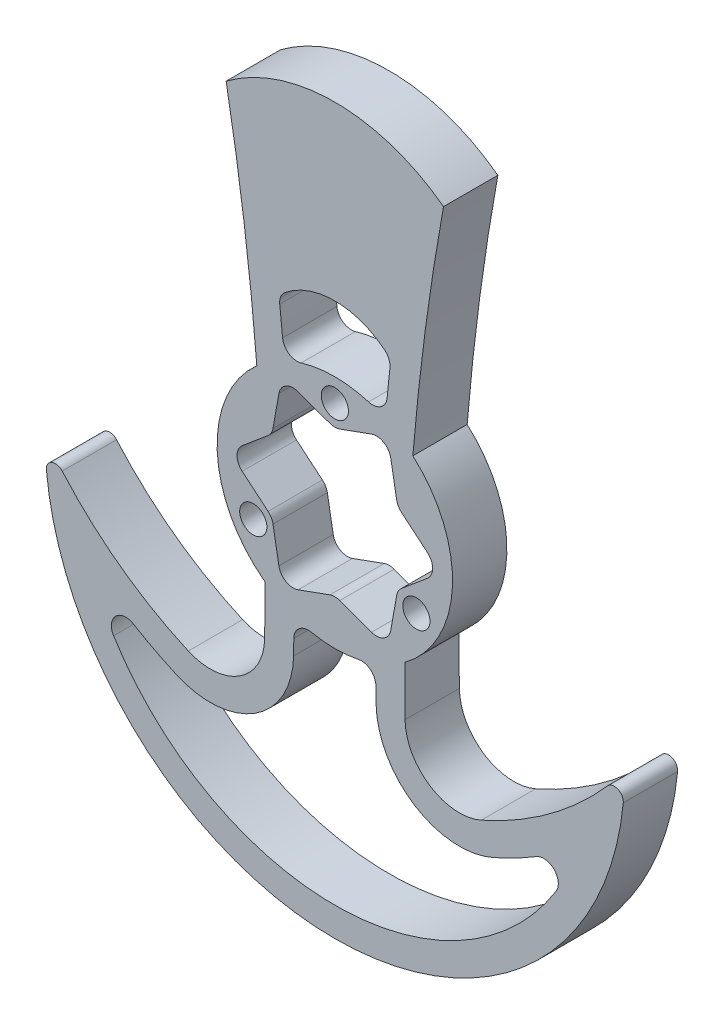
SolidWorks part; units mm, degrees
material "AISI 4340 Steel, annealed"
ref_plane "Front Plane" through (0, 0, 0) normal (0, 0, 1) x (1, 0, 0)
ref_plane "Top Plane" through (0, 0, 0) normal (0, 1, 0) x (1, 0, 0)
ref_plane "Right Plane" through (0, 0, 0) normal (1, 0, 0) x (0, 0, -1)
other "Center of Mass"
sketch "Sketch1" plane through (0, 0, 0) normal (0, 0, 1) x (1, 0, 0)
  line L0 (0, 63.5) -> (0, -63.5) construction
  line L1 (-50.8, -25.4) -> (50.8, -25.4) construction
  line L2 (0, -63.5) -> (36.5351, -63.5) construction
  line L3 (-12.7, 12.7) -> (12.7, 12.7) construction
  line L4 (0, -76.2) -> (0, 50.8) construction
  line L5 (0, 50.8) -> (36.5351, 50.8)
  line L6 (-19.05, 44.45) -> (19.05, 44.45) construction
  line L7 (-12.7, -49.517) -> (-12.7, 12.7) construction
  line L8 (12.7, 12.7) -> (12.7, -49.517) construction
  arc A0 (-50.5616, -30.3161) -> (50.5616, -30.3161) centre (0, -25.4) ccw
  arc A1 (-47.7868, -29.1171) -> (-25.6833, -45.3743) centre (0, 12.7) ccw
  arc A2 (-19.05, 44.45) -> (19.05, 44.45) centre (0, 19.05) cw
  arc A3 (-12.3069, -36.8118) -> (-19.05, 44.45) centre (-427.2497, -30.3329) ccw
  arc A4 (12.3069, -36.8118) -> (19.05, 44.45) centre (427.2497, -30.3329) cw
  arc A7 (25.6833, -45.3743) -> (47.7868, -29.1171) centre (0, 12.7) ccw
  arc A8 (-25.6833, -45.3743) -> (-12.3069, -36.8118) centre (-21.8308, -36.6631) ccw
  arc A9 (7.2275, -36.8911) -> (9.8021, 16.5623) centre (427.2497, -30.3329) cw
  arc A10 (12.3069, -36.8118) -> (25.6833, -45.3743) centre (21.8308, -36.6631) ccw
  arc A12 (-50.5616, -30.3161) -> (-47.7868, -29.1171) centre (-48.9815, -30.1625) cw
  arc A13 (47.7868, -29.1171) -> (50.5616, -30.3161) centre (48.9815, -30.1625) cw
  arc A14 (-7.2275, -36.8911) -> (-9.8021, 16.5623) centre (-427.2497, -30.3329) ccw
  arc A15 (-27.7379, -50.0202) -> (-7.2275, -36.8911) centre (-21.8308, -36.6631) ccw
  arc A16 (-43.1052, -40.64) -> (-27.7379, -50.0202) centre (0, 12.7) ccw
  arc A17 (-43.1052, -40.64) -> (-43.1052, -40.64) centre (-43.1052, -40.64) cw
  arc A18 (-43.1052, -40.64) -> (43.1052, -40.64) centre (0, -25.4) ccw
  arc A19 (43.1052, -40.64) -> (43.1052, -40.64) centre (43.1052, -40.64) cw
  arc A20 (27.7379, -50.0202) -> (43.1052, -40.64) centre (0, 12.7) ccw
  arc A21 (7.2275, -36.8911) -> (27.7379, -50.0202) centre (21.8308, -36.6631) ccw
  arc A22 (-13.4634, 42.0723) -> (13.4634, 42.0723) centre (0, 19.05) cw construction
  arc A23 (-9.8021, 16.5623) -> (9.8021, 16.5623) centre (0, 6.7601) cw
  arc A24 (-7.2275, -36.8911) -> (-13.4634, 42.0723) centre (-427.2497, -30.3329) ccw construction
  arc A25 (7.2275, -36.8911) -> (13.4634, 42.0723) centre (427.2497, -30.3329) cw construction
  point P6 (0, -25.4)
  point P10 (0, 12.7)
  point P15 (50.8, -25.4)
  point P16 (-50.8, -25.4)
  point P18 (0, 44.45)
  dimension "D4" = 127
  dimension "D9" = 9.525
  dimension "D11" = 9.525
  dimension "D12" = 1.5875
  dimension "D13" = 1.5875
  dimension "D1" = 127
  dimension "D2" = 101.6
  dimension "D3" = 38.1
  dimension "D5" = 127
  dimension "D6" = 25.4
  dimension "D7" = 6.35
  dimension "D8" = 38.1
  dimension "D10" = 5.08
extrude "Boss-Extrude1" add sketch "Sketch1" along normal blind 9.525 contours A13 A7 A10 A4 A2 A3 A8 A1 A12 A0 region at (-48.9672, -30.1956, 0)
sketch "Sketch4" plane through (0, 0, 9.525) normal (0, 0, 1) x (1, 0, 0)
  circle A0 centre (0, -11.5279) radius 20.6375
  dimension "D1" = 41.275
extrude "Boss-Extrude3" add sketch "Sketch4" against normal up to surface (9.525 mm away) up to face at (0, -24.1119, 0)
sketch "Sketch2" plane through (0, 0, 9.525) normal (0, 0, 1) x (1, 0, 0)
  line L0 (6.4359, 3.6089) -> (0.8666, 1.5876)
  line L1 (-0.8666, 1.5876) -> (-6.4359, 3.6089)
  line L2 (-9.8035, 1.6647) -> (-10.8376, -4.1692)
  line L3 (-11.7042, -5.6702) -> (-16.2394, -9.4827)
  line L4 (-16.2394, -13.3712) -> (-11.7042, -17.1837)
  line L5 (-10.8376, -18.6847) -> (-9.8035, -24.5186)
  line L6 (-6.4359, -26.4629) -> (-0.8666, -24.4415)
  line L7 (0.8666, -24.4415) -> (6.4359, -26.4629)
  line L8 (9.8035, -24.5186) -> (10.8376, -18.6847)
  line L9 (11.7042, -17.1837) -> (16.2394, -13.3712)
  line L10 (16.2394, -9.4827) -> (11.7042, -5.6702)
  line L11 (10.8376, -4.1692) -> (9.8035, 1.6647)
  line L12 (0, 1.4352) -> (0, -24.2891) construction
  line L13 (-17.145, -11.427) -> (17.145, -11.427) construction
  line L14 (0, 0) -> (0, -11.427) construction
  circle A2 centre (14.2981, -19.682) radius 2.3813
  arc A3 (9.8035, 1.6647) -> (6.4359, 3.6089) centre (7.3025, 1.2213) ccw
  arc A4 (-0.8666, 1.5876) -> (0.8666, 1.5876) centre (0, 3.9752) ccw
  arc A5 (-6.4359, 3.6089) -> (-9.8035, 1.6647) centre (-7.3025, 1.2213) ccw
  arc A6 (-11.7042, -5.6702) -> (-10.8376, -4.1692) centre (-13.3386, -3.7259) ccw
  arc A7 (-16.2394, -9.4827) -> (-16.2394, -13.3712) centre (-14.605, -11.427) ccw
  arc A8 (-10.8376, -18.6847) -> (-11.7042, -17.1837) centre (-13.3386, -19.128) ccw
  arc A9 (-9.8035, -24.5186) -> (-6.4359, -26.4629) centre (-7.3025, -24.0753) ccw
  arc A10 (0.8666, -24.4415) -> (-0.8666, -24.4415) centre (0, -26.8291) ccw
  arc A11 (6.4359, -26.4629) -> (9.8035, -24.5186) centre (7.3025, -24.0753) ccw
  arc A12 (11.7042, -17.1837) -> (10.8376, -18.6847) centre (13.3386, -19.128) ccw
  arc A13 (16.2394, -13.3712) -> (16.2394, -9.4827) centre (14.605, -11.427) ccw
  arc A14 (10.8376, -4.1692) -> (11.7042, -5.6702) centre (13.3386, -3.7259) ccw
  circle A15 centre (0, -11.427) radius 16.51 construction
  circle A16 centre (-14.2981, -19.682) radius 2.3813
  circle A17 centre (0, 5.083) radius 2.3813
  point P48 (0, -11.427)
  point P54 (0, -11.427)
  dimension "D1" = 11.427
  dimension "D2" = 3
extrude "Cut-Extrude1" cut sketch "Sketch2" against normal through all
fillet "Fillet1" radius 2.54 2 edges at (43.1052, -40.64, 4.7625) (-43.1052, -40.64, 4.7625)
fillet "Fillet2" radius 2.54 1 edges at (-7.1767, -30.8774, 4.7625)
fillet "Fillet3" radius 2.54 1 edges at (7.1767, -30.8774, 4.7625)
fillet "Fillet4" radius 2.54 1 edges at (-8.849, 7.1162, 4.7625)
fillet "Fillet5" radius 2.54 1 edges at (-9.8021, 16.5623, 4.7625)
fillet "Fillet6" radius 2.54 1 edges at (9.8021, 16.5623, 4.7625)
fillet "Fillet7" radius 2.54 1 edges at (8.849, 7.1162, 4.7625)
